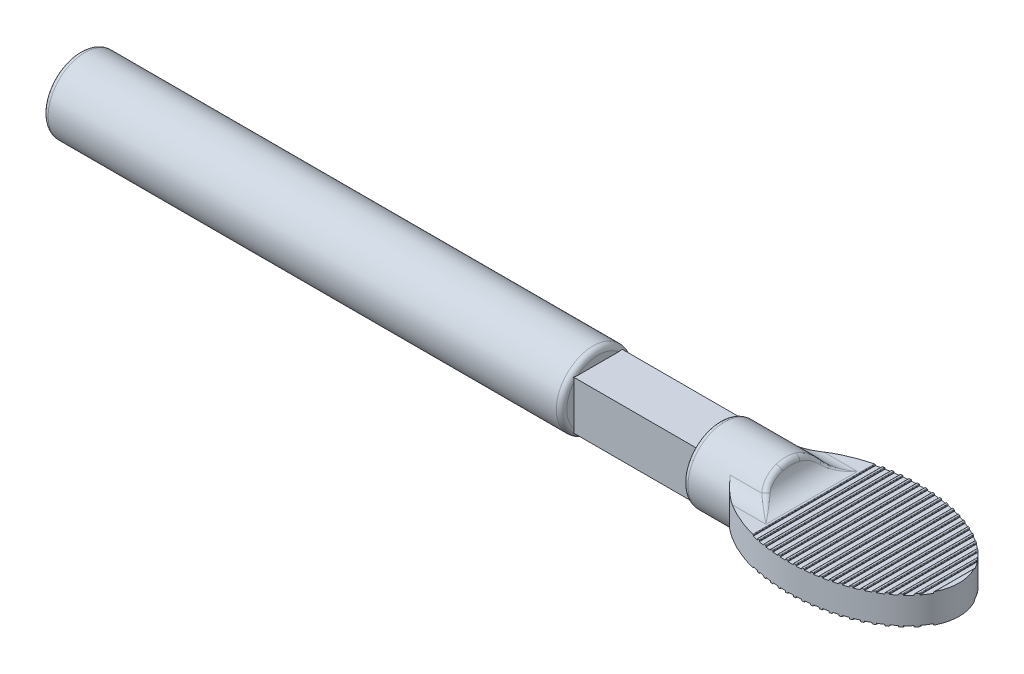
SolidWorks part; units mm, degrees
ref_plane "Front Plane" through (0, 0, 0) normal (0, 0, 1) x (1, 0, 0)
ref_plane "Top Plane" through (0, 0, 0) normal (0, 1, 0) x (1, 0, 0)
ref_plane "Right Plane" through (0, 0, 0) normal (1, 0, 0) x (0, 0, -1)
sketch "Sketch1" plane through (0, 0, 0) normal (1, 0, 0) x (0, 0, -1)
  circle A0 centre (0, 0) radius 3.5
  dimension "D1" = 7
extrude "Boss-Extrude1" add sketch "Sketch1" along normal blind 67.5
sketch "Sketch2" plane through (0, 0, 0) normal (1, 0, 0) x (0, 0, -1)
  line L1 (2.2981, 2.2981) -> (-2.2981, 2.2981)
  line L2 (2.2981, 2.2981) -> (2.2981, -2.2981)
  line L3 (2.2981, -2.2981) -> (-2.2981, -2.2981)
  line L4 (-2.2981, 2.2981) -> (-2.2981, -2.2981)
  line L5 (2.2981, 2.2981) -> (-2.2981, -2.2981) construction
  line L6 (2.2981, -2.2981) -> (-2.2981, 2.2981) construction
  point P0 (0, 0)
  dimension "D1" = 6.5
extrude "Cut-Extrude1" cut sketch "Sketch2" against normal mid plane 11.5 from offset 55 flip side to cut contours L1 L4 L3 L2 | L4 L3 L2 L1 region at (0, 0, 0)
sketch "Sketch3" plane through (0, 0, 0) normal (0, 1, 0) x (1, 0, 0)
  line L0 (0, 0) -> (87.7177, 0) construction
  ellipse E0 centre (73.5, 0) end of major axis (83.5, 0) minor radius 6.25
  point P4 (0, 0)
  point P10 (0, 0)
  point P11 (0, 0)
  point P12 (0, 0)
  dimension "D1" = 20
  dimension "D2" = 12.5
  dimension "D3" = 83.5
extrude "Boss-Extrude2" add sketch "Sketch3" along normal mid plane 2.75
fillet "Fillet1" radius 2 6 edges at (66.214, 1.375, -3.2186) (67.5, 1.375, 0) (66.214, 1.375, 3.2186) (66.214, -1.375, 3.2186) (67.5, -1.375, 0) (66.214, -1.375, -3.2186)
fillet "Fillet2" radius 0.5 10 edges at (68.621, 1.5785, -3.4637) (67.5415, 2.9694, -1.8527) (68.621, 1.5785, 3.4637) (67.6351, 2.6523, 2.2837) (68.621, -1.5785, 3.4637) (67.5415, -2.9694, 1.8527) (68.621, -1.5785, -3.4637) (67.6351, -2.6523, -2.2837) (67.5, 3.5, 0) (67.5, -3.5, 0)
sketch "Sketch4" plane through (0, 0, 0) normal (0, 0, 1) x (1, 0, 0)
  line L0 (83.5, 1.375) -> (66.3083, 1.375) construction
  line L1 (82.5, 1.375) -> (83, 1.375)
  line L2 (82.5, 1.375) -> (82.5, 1.25)
  line L3 (82.5, 1.25) -> (83, 1.25)
  line L4 (83, 1.375) -> (83, 1.25)
  line L5 (83.5, 0) -> (80.9282, 0) construction
  line L7 (82.5, -1.375) -> (82.5, -1.25)
  line L8 (82.5, -1.25) -> (83, -1.25)
  line L9 (83, -1.375) -> (83, -1.25)
  line L10 (83.5, -1.375) -> (83.5, 1.375) construction
  line L11 (82.5, -1.375) -> (83, -1.375)
  line L12 (66.3083, -1.375) -> (83.5, -1.375) construction
  dimension "D1" = 0.5
  dimension "D2" = 0.5
  dimension "D3" = 2.5
extrude "Cut-Extrude2" cut sketch "Sketch4" against normal mid plane 22.75
fillet "Fillet3" radius 0.05 4 edges at (83, -1.375, 0) (82.5, -1.375, 0) (83, 1.375, 0) (82.5, 1.375, 0)
pattern_linear "LPattern1" count 18 spacing 0.75 along (-1, 0, 0) of "Fillet3", "Cut-Extrude2"
fillet "Fillet4" radius 0.5 3 edges at (0, 0, -3.5) (49.25, 0, -3.5) (60.75, 0, -3.5)
